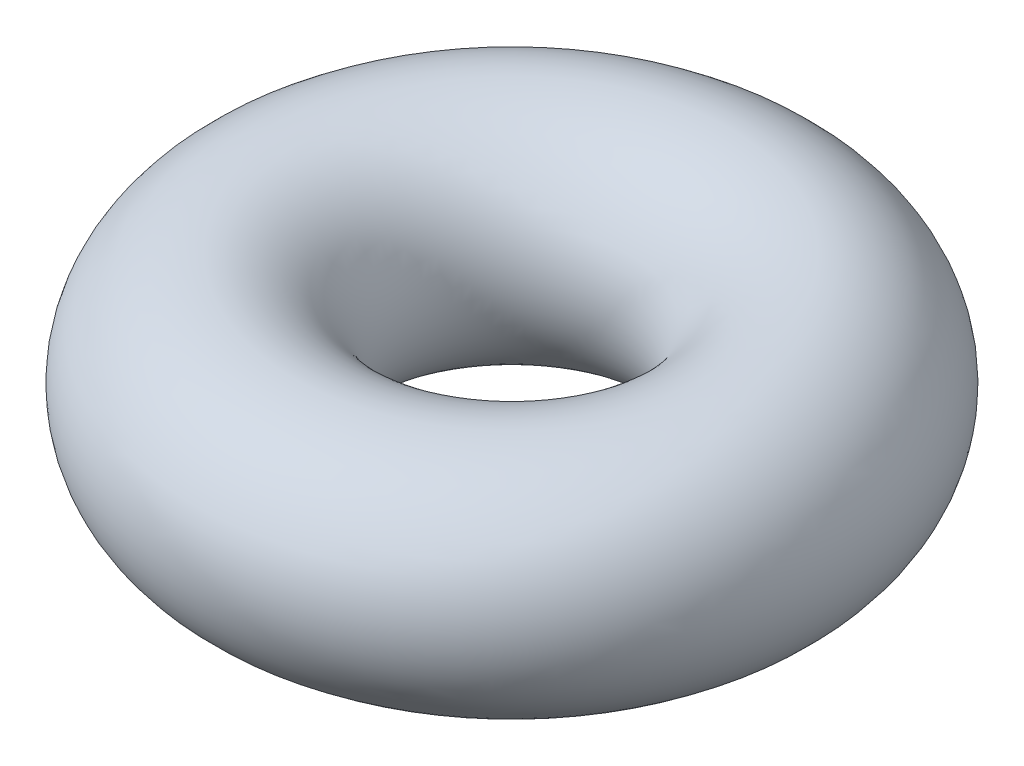
SolidWorks part; units mm, degrees
ref_plane "Front Plane" through (0, 0, 0) normal (0, 0, 1) x (1, 0, 0)
ref_plane "Top Plane" through (0, 0, 0) normal (0, 1, 0) x (1, 0, 0)
ref_plane "Right Plane" through (0, 0, 0) normal (1, 0, 0) x (0, 0, -1)
sketch "Sketch1" plane through (0, 0, 0) normal (0, 0, 1) x (1, 0, 0)
  line L0 (-0.7112, 0) -> (0.7112, 0) construction
  line L1 (-2.2352, 0) -> (2.2352, 0) construction
  circle A0 centre (-1.4732, 0) radius 0.762 construction
  dimension "Width" = 1.524
  dimension "ID" = 1.4224
  dimension "OD" = 4.4704
sketch "Sketch3" plane through (0, 0, 0) normal (1, 0, 0) x (0, 0, -1)
  line L0 (0, 0) -> (-0.4741, 0) construction
  line L1 (-0.4741, 0) -> (-0.4741, 0.762) construction
  point P0 (-0.4741, 0.762)
  dimension "D1" = 0.4741
  dimension "D2" = 0.762
sketch "Sketch2" plane through (0, 0, 0) normal (0, 0, 1) x (1, 0, 0)
  line L0 (0, 0) -> (0, 0.762) construction
  line L1 (-0.7112, 0) -> (0.7112, 0) construction
  circle A0 centre (-1.4732, 0) radius 0.762 construction
  circle A1 centre (-1.4732, 0) radius 0.762
  point P7 (-1.4732, 0.762)
revolve "Revolve1" add sketch "Sketch2" angle 360 about L0
ref_axis "Center Axis 1" through (0, 0.9779, 0) along (0, -1, 0)
equation "\"D1@Sketch3\"=\"ID@Sketch1\"/3"
equation "\"D2@Sketch3\"=\"Width@Sketch1\"/2"
